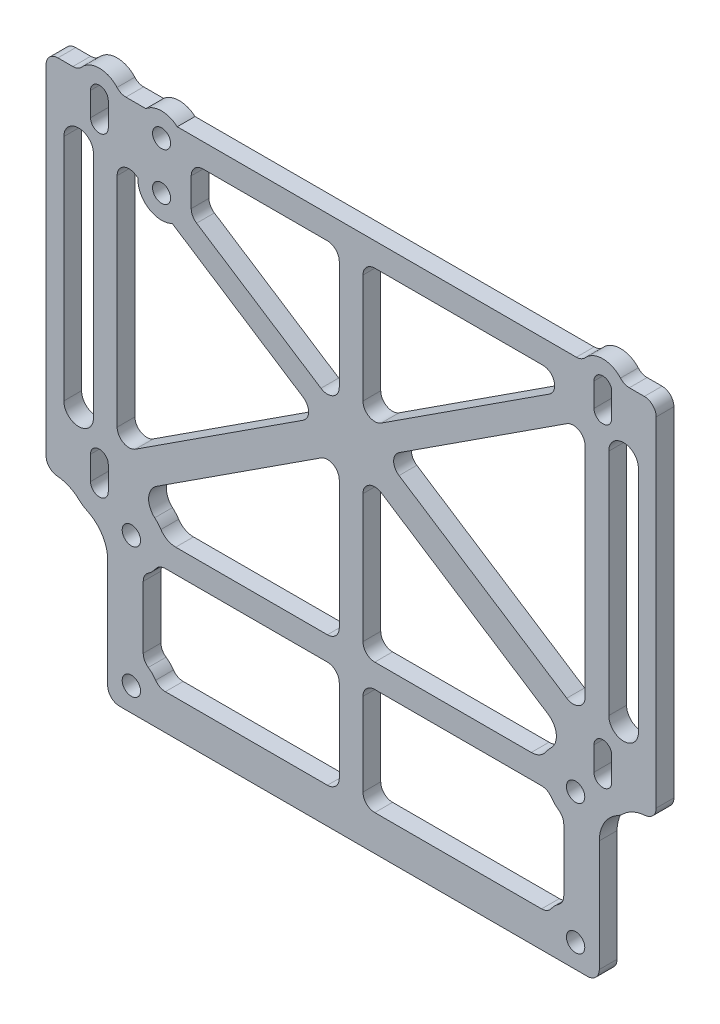
SolidWorks part; units mm, degrees
material "Thornel Mat VMA"
ref_plane "前视基准面" through (0, 0, 0) normal (0, 0, 1) x (1, 0, 0)
ref_plane "上视基准面" through (0, 0, 0) normal (0, 1, 0) x (1, 0, 0)
ref_plane "右视基准面" through (0, 0, 0) normal (1, 0, 0) x (0, 0, -1)
sketch "草图1" plane through (0, 0, 0) normal (0, 0, 1) x (1, 0, 0)
  line L1 (51.5, -30.6) -> (-51.5, -30.6)
  line L2 (51.5, -30.6) -> (51.5, 30.6)
  line L3 (51.5, 30.6) -> (-51.5, 30.6)
  line L4 (-51.5, -30.6) -> (-51.5, 30.6)
  line L5 (51.5, -30.6) -> (-51.5, 30.6) construction
  line L6 (51.5, 30.6) -> (-51.5, -30.6) construction
  point P0 (0, 0)
  dimension "D1" = 61.2
  dimension "D2" = 103
extrude "凸台-拉伸1" add sketch "草图1" along normal blind 3
sketch "草图2" plane through (0, 0, 0) normal (0, 0, -1) x (-1, 0, 0)
  line L0 (-42.5, 27.6) -> (0, 0) construction
  line L1 (0, 0) -> (42.5, -27.6) construction
  line L2 (-42.5, 27.6) -> (-42.5, -27.6) construction
  line L4 (42.5, 27.6) -> (42.5, -27.6) construction
  line L5 (42.5, 27.6) -> (0, 0) construction
  line L6 (-42.5, 27.6) -> (42.5, 27.6) construction
  line L7 (0, 0) -> (-42.5, -27.6) construction
  line L8 (-42.5, -27.6) -> (42.5, -27.6) construction
  line L9 (-39.5, 22.0747) -> (-39.5, -22.0747)
  line L10 (-5.5082, 0) -> (-39.5, -22.0747)
  line L11 (-39.5, 22.0747) -> (-5.5082, 0)
  line L12 (-32.3722, 24.6) -> (32.3722, 24.6) construction
  line L13 (32.3722, 24.6) -> (0, 3.5771) construction
  line L14 (-32.3722, 24.6) -> (0, 3.5771) construction
  line L15 (0, -2.3847) -> (-35.7481, -25.6)
  line L16 (-35.7481, -25.6) -> (35.7481, -25.6)
  line L17 (0, -2.3847) -> (35.7481, -25.6)
  line L18 (39.5, 22.0747) -> (5.5082, 0)
  line L19 (5.5082, 0) -> (39.5, -22.0747)
  line L20 (39.5, 22.0747) -> (39.5, -22.0747)
  line L21 (-46, 19.6) -> (-46, -19.06) construction
  line L22 (-43.5, 19.6) -> (-43.5, -19.06)
  line L23 (-48.5, 19.6) -> (-48.5, -19.06)
  line L24 (-51.5, -30.6) -> (-51.5, 30.6) construction
  line L25 (0, 0) -> (0, 50000) construction
  line L26 (46, 19.6) -> (46, -19.06) construction
  line L27 (43.5, 19.6) -> (43.5, -19.06)
  line L28 (48.5, 19.6) -> (48.5, -19.06)
  line L29 (32, 38.7242) -> (32, -49961.2758) construction
  line L30 (-51.5, 30.6) -> (51.5, 30.6) construction
  circle A0 centre (-42.5, 27.6) radius 1.5 construction
  circle A1 centre (-42.5, -27.6) radius 1.5 construction
  circle A2 centre (42.5, -27.6) radius 1.5 construction
  circle A3 centre (42.5, 27.6) radius 1.5 construction
  circle A4 centre (-42.5, 27.6) radius 1.5
  circle A5 centre (-42.5, -27.6) radius 1.5
  circle A6 centre (42.5, -27.6) radius 1.5
  circle A7 centre (42.5, 27.6) radius 1.5
  arc A8 (-43.5, 19.6) -> (-48.5, 19.6) centre (-46, 19.6) ccw
  arc A9 (-48.5, -19.06) -> (-43.5, -19.06) centre (-46, -19.06) ccw
  arc A10 (43.5, 19.6) -> (48.5, 19.6) centre (46, 19.6) cw
  arc A11 (48.5, -19.06) -> (43.5, -19.06) centre (46, -19.06) cw
  circle A12 centre (32, 27.6) radius 1.525
  circle A13 centre (32, 19.6) radius 1.525
  point P28 (-46, 0.27)
  point P39 (46, 0.27)
  dimension "D10" = 3.05
  dimension "D5" = 3
  dimension "D6" = 4
  dimension "D7" = 8
  dimension "D8" = 8.54
  dimension "D9" = 32
  dimension "D11" = 8
  dimension "D12" = 3
  dimension "D1" = 3
  dimension "D2" = 3
  dimension "D3" = 2
  dimension "D4" = 3
extrude "切除-拉伸1" cut sketch "草图2" against normal blind 10
sketch "草图3" plane through (0, 0, 3) normal (0, 0, 1) x (1, 0, 0)
  line L0 (0.4, 0.0878) -> (0.4, -49940.3858) construction
  line L1 (-41.1, -30.6) -> (-41.1, -59)
  line L2 (-51.5, -30.6) -> (51.5, -30.6) construction
  line L3 (-41.1, -59) -> (41.9, -59)
  line L6 (41.9, -59) -> (41.9, -30.6)
  line L7 (41.9, -30.6) -> (-41.1, -30.6)
  circle A0 centre (-37.1, -33) radius 1.55
  circle A1 centre (-37.1, -55) radius 1.55
  circle A2 centre (37.9, -55) radius 1.55
  circle A3 centre (37.9, -33) radius 1.55
  point P18 (0, -30.6)
  point P19 (0.4, -59)
  dimension "D3" = 3.1
  dimension "D1" = 22
  dimension "D2" = 0.4
  dimension "D4" = 33
  dimension "D5" = 4
  dimension "D6" = 4
  dimension "D7" = 75
  dimension "D8" = 4
extrude "凸台-拉伸2" add sketch "草图3" against normal up to surface (3 mm away) up to face at (-28.1694, 0, 0)
sketch "草图10" plane through (0, 0, 0) normal (0, 0, -1) x (-1, 0, 0)
  line L0 (-39.1241, 26.6) -> (27, 26.6)
  line L1 (27, 26.6) -> (27, 18.7265)
  line L2 (27, 18.7265) -> (0, 1.1924)
  line L3 (0, 1.1924) -> (-39.1241, 26.6)
  line L4 (-5.5082, 0) -> (-39.5, 22.0747) construction
  line L5 (39.5, 22.0747) -> (5.5082, 0) construction
  line L6 (-51.5, 30.6) -> (51.5, 30.6) construction
  circle A0 centre (32, 27.6) radius 1.525 construction
  dimension "D1" = 4
  dimension "D2" = 4
  dimension "D3" = 5
extrude "切除-拉伸5" cut sketch "草图10" against normal blind 10
fillet "圆角1" radius 2 17 edges at (-51.5, 30.6, 1.5) (51.5, -30.6, 1.5) (-51.5, -30.6, 1.5) (51.5, 30.6, 1.5) (5.5082, 0, 1.5) (-39.5, -22.0747, 1.5) (-5.5082, 0, 1.5) (-39.5, 22.0747, 1.5) (-35.7481, -25.6, 1.5) (35.7481, -25.6, 1.5) (0, -2.3847, 1.5) (39.5, -22.0747, 1.5) (39.5, 22.0747, 1.5) (-27, 26.6, 1.5) (-27, 18.7265, 1.5) (0, 1.1924, 1.5) (39.1241, 26.6, 1.5)
sketch "草图4" plane through (0, 0, 3) normal (0, 0, 1) x (1, 0, 0)
  line L0 (-37.1, -33) -> (-37.1, -55) construction
  line L1 (-37.1, -55) -> (37.9, -55) construction
  line L2 (37.9, -55) -> (37.9, -33) construction
  line L3 (37.9, -33) -> (-37.1, -33) construction
  line L4 (-35.1, -35) -> (-35.1, -53)
  line L5 (-35.1, -53) -> (35.9, -53)
  line L6 (35.9, -53) -> (35.9, -35)
  line L7 (35.9, -35) -> (-35.1, -35)
  circle A0 centre (-37.1, -33) radius 5
  circle A1 centre (-37.1, -55) radius 5
  circle A2 centre (37.9, -33) radius 5
  circle A3 centre (37.9, -55) radius 5
  dimension "D2" = 10
  dimension "D1" = 2
extrude "切除-拉伸2" cut sketch "草图4" against normal blind 10 contours A3 L6 A2 L7 A0 L4 A1 L5
fillet "圆角3" radius 2 8 edges at (33.3174, -53, 1.5) (-32.5174, -53, 1.5) (-35.1, -50.4174, 1.5) (-35.1, -37.5826, 1.5) (33.3174, -35, 1.5) (35.9, -37.5826, 1.5) (35.9, -50.4174, 1.5) (-32.5174, -35, 1.5)
sketch "草图6" plane through (0, 0, 3) normal (0, 0, 1) x (1, 0, 0)
  line L0 (-42.5, 27.6) -> (-42.5, -27.6) construction
  line L1 (0, 0) -> (0, 50000) construction
  line L2 (-42.5, 28.6) -> (-42.5, 24.6) construction
  line L3 (-41, 28.6) -> (-41, 24.6)
  line L4 (-44, 28.6) -> (-44, 24.6)
  line L5 (0, 0) -> (-50000, 0) construction
  line L6 (49.5, 30.6) -> (-49.5, 30.6) construction
  line L7 (-42.5, -28.6) -> (-42.5, -24.6) construction
  line L8 (-41, -28.6) -> (-41, -24.6)
  line L9 (-44, -28.6) -> (-44, -24.6)
  line L10 (42.5, 27.6) -> (42.5, -27.6) construction
  line L11 (42.5, -28.6) -> (42.5, -24.6) construction
  line L12 (41, -28.6) -> (41, -24.6)
  line L13 (44, -28.6) -> (44, -24.6)
  line L14 (42.5, 28.6) -> (42.5, 24.6) construction
  line L15 (41, 28.6) -> (41, 24.6)
  line L16 (44, 28.6) -> (44, 24.6)
  arc A0 (-41, 28.6) -> (-44, 28.6) centre (-42.5, 28.6) ccw
  arc A1 (-44, 24.6) -> (-41, 24.6) centre (-42.5, 24.6) ccw
  circle A2 centre (-42.5, 27.6) radius 1.5 construction
  arc A3 (-41, -28.6) -> (-44, -28.6) centre (-42.5, -28.6) cw
  arc A4 (-44, -24.6) -> (-41, -24.6) centre (-42.5, -24.6) cw
  arc A5 (41, -28.6) -> (44, -28.6) centre (42.5, -28.6) ccw
  arc A6 (44, -24.6) -> (41, -24.6) centre (42.5, -24.6) ccw
  arc A7 (41, 28.6) -> (44, 28.6) centre (42.5, 28.6) cw
  arc A8 (44, 24.6) -> (41, 24.6) centre (42.5, 24.6) cw
  point P9 (-42.5, 26.6)
  point P24 (-42.5, -26.6)
  point P33 (42.5, -26.6)
  point P40 (42.5, 26.6)
  dimension "D3" = 1.5
  dimension "D1" = 4
  dimension "D2" = 2
extrude "切除-拉伸3" cut sketch "草图6" against normal blind 10
sketch "草图7" plane through (0, 0, 3) normal (0, 0, 1) x (1, 0, 0)
  line L0 (49.5, 30.6) -> (-49.5, 30.6) construction
  line L1 (49.5, 30.6) -> (-49.5, 30.6)
  line L2 (41.9, -30.6) -> (49.5, -30.6) construction
  line L3 (41.9, -59) -> (41.9, -30.6) construction
  line L4 (-41.1, -30.6) -> (-41.1, -59) construction
  line L5 (-49.5, -30.6) -> (-41.1, -30.6) construction
  line L6 (41.9, -30.6) -> (49.5, -30.6)
  line L7 (41.9, -59) -> (41.9, -30.6)
  line L8 (-41.1, -30.6) -> (-41.1, -59)
  line L9 (-49.5, -30.6) -> (-41.1, -30.6)
  circle A0 centre (-42.5, 28.6) radius 4
  circle A1 centre (42.5, 28.6) radius 4
  circle A2 centre (-42.5, -28.6) radius 5
  circle A3 centre (42.5, -28.6) radius 5
  circle A4 centre (-32, 19.6) radius 4
  circle A5 centre (-32, 27.6) radius 4
  circle A6 centre (-32, 19.6) radius 1.525
  circle A7 centre (-32, 27.6) radius 1.525
  circle A8 centre (-32, 27.6) radius 1.525 construction
  dimension "D1" = 8
  dimension "D2" = 8
  dimension "D3" = 10
extrude "凸台-拉伸3" add sketch "草图7" against normal up to surface (3 mm away) contours L1 A0 | L1 A1 | L9 A2 L8 | L7 A3 L6 | A4 A6 | L1 A5 A7
fillet "圆角2" radius 2 6 edges at (41.9, -59, 1.5) (-41.1, -59, 1.5) (39.0359, 30.6, 1.5) (45.9641, 30.6, 1.5) (-45.9641, 30.6, 1.5) (-39.0359, 30.6, 1.5)
sketch "草图8" plane through (0, 0, 3) normal (0, 0, 1) x (1, 0, 0)
  line L0 (0, 0) -> (0, -50000) construction
  line L1 (0, -2.3847) -> (-38.0111, -27.0696)
  line L2 (-31.4431, -31) -> (0, -31)
  line L4 (32.1554, -35) -> (-31.3554, -35) construction
  line L5 (0, -31) -> (32.2431, -31)
  line L6 (37.9039, -27) -> (0, -2.3847)
  line L8 (30.0856, -21.9227) -> (1.0893, -3.0921) construction
  line L9 (-1.0893, -3.0921) -> (-30.0856, -21.9227) construction
  circle A0 centre (-37.1, -33) radius 6
  circle A1 centre (37.9, -33) radius 6
  point P13 (0, -0.8193)
  point P14 (-35.8037, -28.0079)
  dimension "D2" = 12
  dimension "D3" = 12
  dimension "D1" = 4
extrude "切除-拉伸4" cut sketch "草图8" against normal blind 10 contours L0 L1 A0 L2 | L6 L0 L5 A1
fillet "圆角4" radius 3 5 edges at (37.9039, -27, 1.5) (32.2431, -31, 1.5) (-38.0111, -27.0696, 1.5) (0, -2.3847, 1.5) (-31.4431, -31, 1.5)
fillet "圆角6" radius 6 4 edges at (-47.0826, -30.6, 1.5) (47.0826, -30.6, 1.5) (41.9, -33.5639, 1.5) (-41.1, -33.4, 1.5)
sketch "草图11" plane through (0, 0, 3) normal (0, 0, 1) x (1, 0, 0)
  line L0 (0, 26.6) -> (0, -59) construction
  line L1 (32.3722, 26.6) -> (-25, 26.6) construction
  line L3 (-2, 26.6) -> (-2, -55.7585)
  line L4 (2, 26.6) -> (2, -55.7585)
  line L5 (-2, 26.6) -> (2, 26.6)
  line L6 (-2, -55.7585) -> (2, -55.7585)
  line L7 (0, 26.6) -> (0, -55.7585) construction
  point P4 (0.4, -59)
  point P11 (0, 0)
  dimension "D1" = 2
  dimension "D2" = 2
extrude "凸台-拉伸4" add sketch "草图11" against normal up to surface (3 mm away) up to face at (2.9713, -23.1725, 0)
fillet "圆角7" radius 2 12 edges at (-2, -31, 1.5) (-2, -3.6836, 1.5) (2, -31, 1.5) (2, -3.6836, 1.5) (2, 2.4912, 1.5) (2, 26.6, 1.5) (-2, 2.4912, 1.5) (-2, 26.6, 1.5) (2, -53, 1.5) (2, -35, 1.5) (-2, -53, 1.5) (-2, -35, 1.5)
